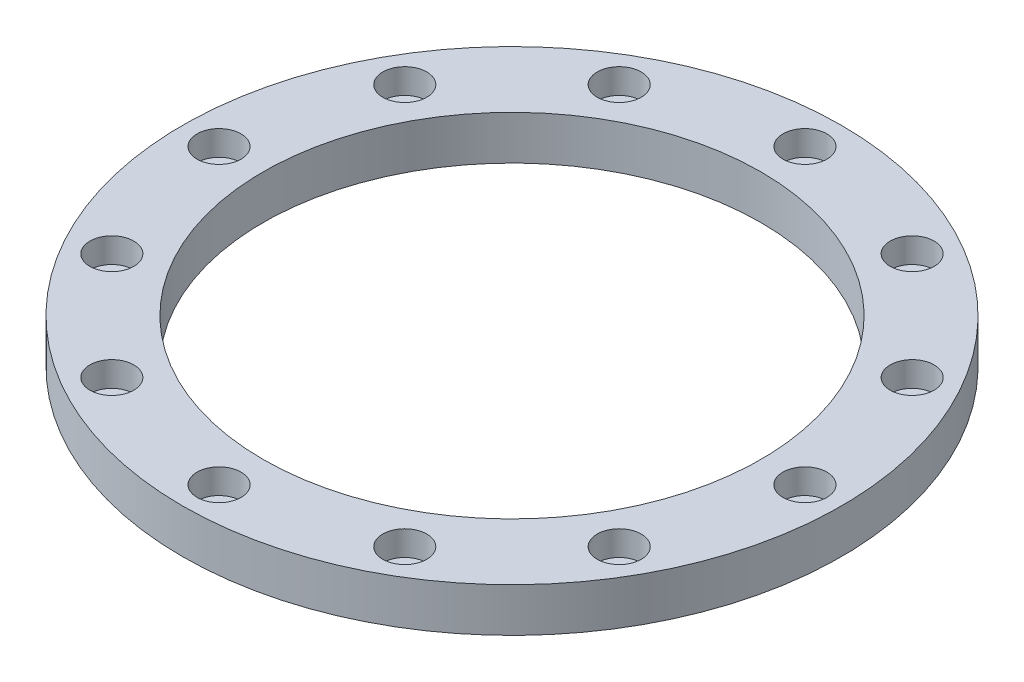
SolidWorks part; units mm, degrees
ref_plane "前视基准面" through (0, 0, 0) normal (0, 0, 1) x (1, 0, 0)
ref_plane "上视基准面" through (0, 0, 0) normal (0, 1, 0) x (1, 0, 0)
ref_plane "右视基准面" through (0, 0, 0) normal (1, 0, 0) x (0, 0, -1)
sketch "草图1" plane through (0, 0, 0) normal (0, 1, 0) x (1, 0, 0)
  circle A0 centre (0, 0) radius 45
  circle A1 centre (0, 0) radius 34
  dimension "D1" = 90
  dimension "D2" = 68
extrude "凸台-拉伸1" add sketch "草图1" along normal blind 6
hole_wizard "打孔尺寸(%根据)内六角圆柱头螺钉的类型1" positions "草图3" profile "草图2" counterbore size "M3" standard "GB" end condition through all
sketch "草图3" plane through (0, 6, 0) normal (0, 1, 0) x (1, 0, 0)
  line L0 (0, 0) -> (0, 48.1748) construction
  circle A0 centre (0, 0) radius 40 construction
  point P0 (0, 40)
  dimension "D1" = 80
sketch "草图2" plane through (0, 6, -40) normal (1, 0, 0) x (0, 0, 1)
  line L0 (0, 0) -> (0, 6)
  line L1 (0, 6) -> (1.8, 6)
  line L3 (1.8, 6) -> (1.8, 3.4)
  line L4 (1.8, 3.4) -> (3, 3.4)
  line L5 (3, 3.4) -> (3, 0)
  line L7 (3, 0) -> (0, 0)
  line L11 (0, -6.35) -> (0, 107.95) construction
  dimension "通孔孔直径" = 3.6
  dimension "通孔孔深度" = 6
  dimension "柱形沉头孔直径" = 6
  dimension "柱形沉头孔深度" = 3.4
ref_axis "基准轴1" through (0, 6, 0) along (0, -1, 0)
pattern_circular "阵列(圆周)1" count 12 over 360 about axis through (0, 6, 0) along (0, -1, 0) of "打孔尺寸(%根据)内六角圆柱头螺钉的类型1"
